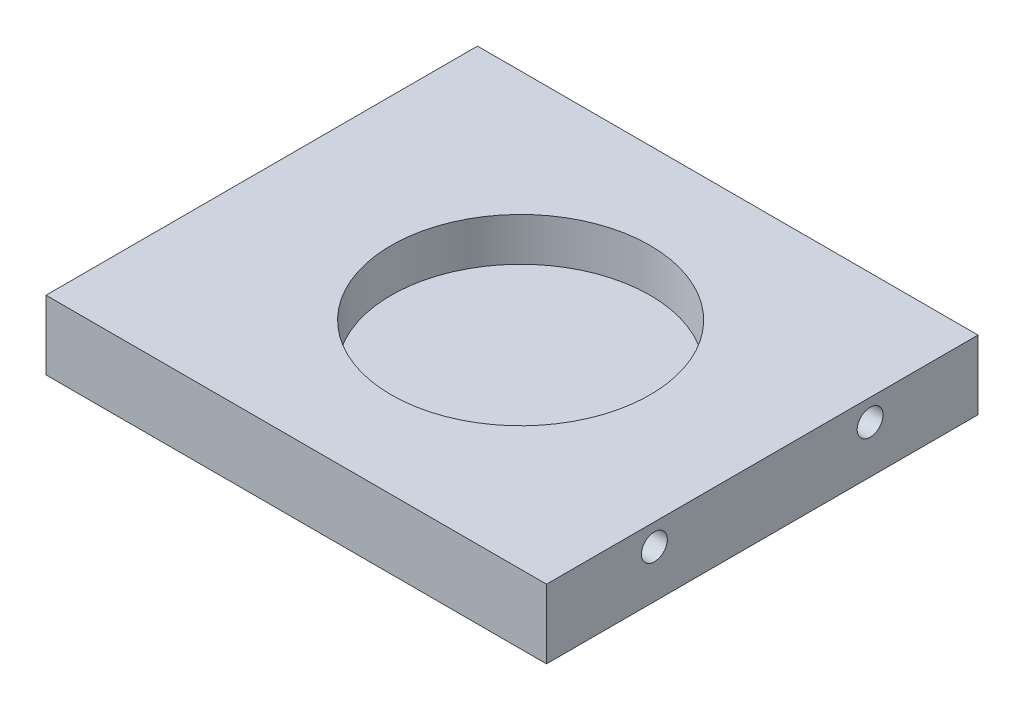
SolidWorks part; units mm, degrees
ref_plane "Plan de face" through (0, 0, 0) normal (0, 0, 1) x (1, 0, 0)
ref_plane "Plan de dessus" through (0, 0, 0) normal (0, 1, 0) x (1, 0, 0)
ref_plane "Plan de droite" through (0, 0, 0) normal (1, 0, 0) x (0, 0, -1)
sketch "Esquisse1" plane through (0, 0, 0) normal (0, 0, 1) x (1, 0, 0)
  line L0 (-5.5, -49) -> (52.5, -49) construction
  line L5 (-5.5, -45) -> (52.5, -45)
  line L6 (-5.5, -45) -> (-5.5, -53)
  line L7 (-5.5, -53) -> (52.5, -53)
  line L8 (52.5, -45) -> (52.5, -53)
  line L9 (23.5, -45) -> (23.5, -53) construction
  dimension "D1" = 8
  dimension "D2" = 58
extrude "Boss.-Extru.1" add sketch "Esquisse1" along normal blind 50 contours L5 | L7 L8 L5 L6
sketch "Esquisse2" plane through (0, -45, 0) normal (0, 1, 0) x (-1, 0, 0)
  line L0 (5.5, 50) -> (-52.5, 50) construction
  line L7 (-52.5, 50) -> (-52.5, 0) construction
  circle A0 centre (-24.5, 25) radius 15
  dimension "D10" = 28
  dimension "D11" = 25
extrude "Enlèv. mat.-Extru.1" cut sketch "Esquisse2" against normal blind 5
sketch "Esquisse3" plane through (-5.5, 0, 0) normal (-1, 0, 0) x (0, 0, 1)
  line L0 (50, -53) -> (0, -53) construction
  line L1 (0, -45) -> (0, -53) construction
  line L2 (50, -45) -> (50, -53) construction
  circle A0 centre (12.5, -47.5) radius 1.5
  circle A1 centre (37.5, -47.5) radius 1.5
  dimension "D1" = 5.5
  dimension "D2" = 5.5
  dimension "D3" = 12.5
  dimension "D4" = 12.5
extrude "Enlèv. mat.-Extru.2" cut sketch "Esquisse3" against normal blind 10
sketch "Esquisse4" plane through (52.5, 0, 0) normal (1, 0, 0) x (0, 0, -1)
  line L0 (-50, -53) -> (0, -53) construction
  line L1 (-50, -45) -> (-50, -53) construction
  line L2 (0, -45) -> (0, -53) construction
  circle A0 centre (-37.5, -47.5) radius 1.5
  circle A1 centre (-12.5, -47.5) radius 1.5
  dimension "D1" = 5.5
  dimension "D2" = 5.5
  dimension "D3" = 12.5
  dimension "D4" = 12.5
extrude "Enlèv. mat.-Extru.3" cut sketch "Esquisse4" against normal blind 10
